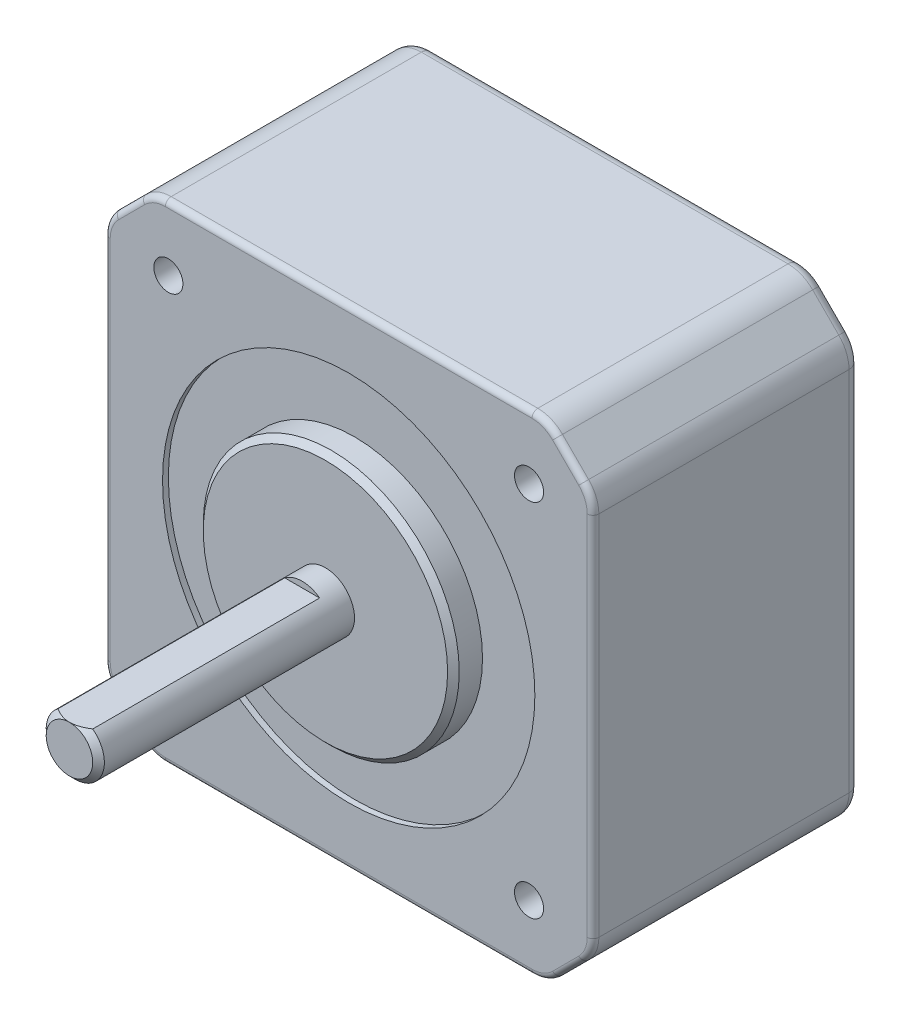
SolidWorks part; units mm, degrees
material "Commercially Pure CP-Ti UNS R50400 (SS)"
ref_plane "Front Plane" through (0, 0, 0) normal (0, 0, 1) x (1, 0, 0)
ref_plane "Top Plane" through (0, 0, 0) normal (0, 1, 0) x (1, 0, 0)
ref_plane "Right Plane" through (0, 0, 0) normal (1, 0, 0) x (0, 0, -1)
sketch "Sketch1" plane through (0, 0, 0) normal (0, 0, 1) x (1, 0, 0)
  line L1 (-21, -21) -> (21, -21)
  line L2 (-21, -21) -> (-21, 21)
  line L3 (-21, 21) -> (21, 21)
  line L4 (21, -21) -> (21, 21)
  line L5 (-21, -21) -> (21, 21) construction
  line L6 (-21, 21) -> (21, -21) construction
  point P0 (0, 0)
  dimension "D1" = 42
  dimension "D2" = 42
extrude "Boss-Extrude1" add sketch "Sketch1" along normal mid plane 23
chamfer "Chamfer1" distance 4 angle 45 4 edges at (-21, -21, 0) (21, -21, 0) (-21, 21, 0) (21, 21, 0)
sketch "Sketch2" plane through (0, 0, 11.5) normal (0, 0, 1) x (1, 0, 0)
  circle A0 centre (0, 0) radius 11
  dimension "D1" = 22
extrude "Boss-Extrude2" add sketch "Sketch2" along normal blind 2
sketch "Sketch3" plane through (0, 0, 11.5) normal (0, 0, 1) x (1, 0, 0)
  circle A0 centre (0, 0) radius 16
  circle A1 centre (0, 0) radius 11
  dimension "D1" = 32
extrude "Cut-Extrude1" cut sketch "Sketch3" against normal blind 0.5
sketch "Sketch4" plane through (0, 0, 13.5) normal (0, 0, 1) x (1, 0, 0)
  circle A0 centre (0, 0) radius 2.5
  dimension "D1" = 5
extrude "Boss-Extrude3" add sketch "Sketch4" along normal blind 22
sketch "Sketch5" plane through (0, 0, 35.5) normal (0, 0, 1) x (1, 0, 0)
  line L1 (-4.4436, 2) -> (5.9206, 2)
  line L2 (-4.4436, 2) -> (-4.4436, 3.526)
  line L3 (-4.4436, 3.526) -> (5.9206, 3.526)
  line L4 (5.9206, 2) -> (5.9206, 3.526)
  dimension "D1" = 2
extrude "Cut-Extrude2" cut sketch "Sketch5" against normal blind 20
hole_wizard "M3x0.5 Tapped Hole1" positions "Sketch6" profile "Sketch7" tap size "M3x0.5" standard "ANSI Metric"
sketch "Sketch6" plane through (0, 0, 11.5) normal (0, 0, 1) x (1, 0, 0)
  point P0 (-15.5, 15.5)
  dimension "D1" = 15.5
  dimension "D2" = 15.5
sketch "Sketch7" plane through (-15.5, 15.5, 11.5) normal (1, 0, 0) x (0, -1, 0)
  line L0 (0, 0) -> (0, 8.2511)
  line L1 (0, 8.2511) -> (1.25, 7.5)
  line L2 (1.25, 7.5) -> (1.25, 0)
  line L5 (1.25, 0) -> (0, 0)
  line L10 (0, 8.2511) -> (-1.25, 7.5) construction
  line L11 (0, -6.35) -> (0, 107.95) construction
  dimension "Tap Drill Dia." = 2.5
  dimension "Tap Drill Depth" = 7.5
  dimension "Drill Angle" = 118
cosmetic thread "Hole Thread1" parameters "D1"=6, "D2"=3
pattern_circular "CirPattern1" count 4 over 360 about axis through (0, 0, 13.5) along (0, 0, -1) of "M3x0.5 Tapped Hole1"
fillet "Fillet1" radius 3 8 edges at (-21, -17, 0) (-17, -21, 0) (17, -21, 0) (21, -17, 0) (21, 17, 0) (17, 21, 0) (-21, 17, 0) (-17, 21, 0)
chamfer "Chamfer2" distance 0.5 angle 45 2 edges at (0, -2.5, 35.5) (11, 0, 13.5)
fillet "Fillet2" radius 1 16 edges at (16.9054, 20.7716, -11.5) (19, 19, -11.5) (20.7716, 16.9054, -11.5) (21, 0, -11.5) (20.7716, -16.9054, -11.5) (19, -19, -11.5) (16.9054, -20.7716, -11.5) (0, -21, -11.5) (-16.9054, -20.7716, -11.5) (-19, -19, -11.5) (-20.7716, -16.9054, -11.5) (-21, 0, -11.5) (-20.7716, 16.9054, -11.5) (-19, 19, -11.5) (-16.9054, 20.7716, -11.5) (0, 21, -11.5)
fillet "Fillet3" radius 0.5 16 edges at (16.9054, 20.7716, 11.5) (19, 19, 11.5) (20.7716, 16.9054, 11.5) (21, 0, 11.5) (20.7716, -16.9054, 11.5) (19, -19, 11.5) (16.9054, -20.7716, 11.5) (0, -21, 11.5) (-16.9054, -20.7716, 11.5) (-19, -19, 11.5) (-20.7716, -16.9054, 11.5) (-21, 0, 11.5) (-20.7716, 16.9054, 11.5) (-19, 19, 11.5) (-16.9054, 20.7716, 11.5) (0, 21, 11.5)
sketch "Sketch9" plane through (0, 0, -11.5) normal (0, 0, -1) x (-1, 0, 0)
  circle A0 centre (0, 0) radius 3.5
  dimension "D1" = 7
extrude "Cut-Extrude3" cut sketch "Sketch9" against normal blind 3.5
